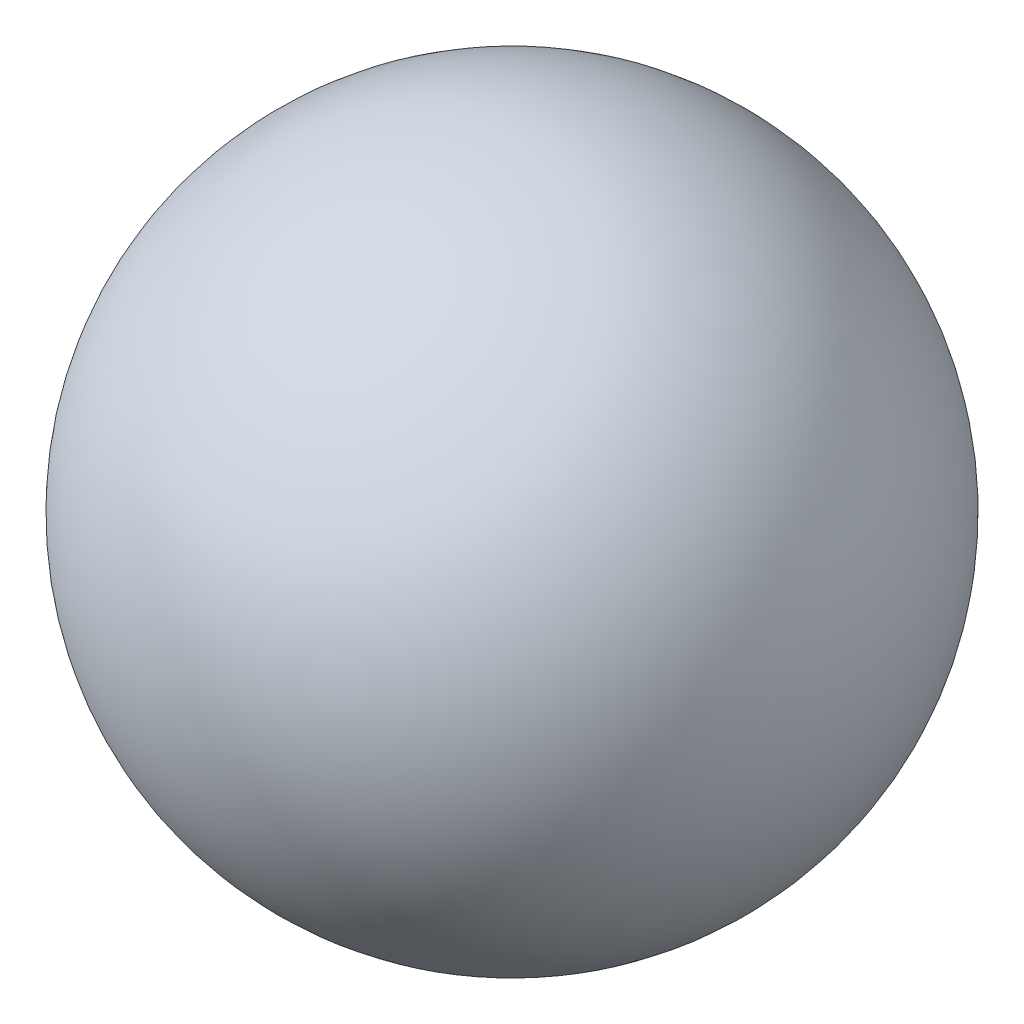
SolidWorks part; units mm, degrees
ref_plane "Front Plane" through (0, 0, 0) normal (0, 0, 1) x (1, 0, 0)
ref_plane "Top Plane" through (0, 0, 0) normal (0, 1, 0) x (1, 0, 0)
ref_plane "Right Plane" through (0, 0, 0) normal (1, 0, 0) x (0, 0, -1)
sketch "Sketch1" plane through (0, 0, 0) normal (1, 0, 0) x (0, 0, -1)
  line L0 (0, 20) -> (0, -20)
  arc A0 (0, 20) -> (0, -20) centre (0, 0) cw
  dimension "D1" = 20
revolve "Revolve1" add sketch "Sketch1" angle 360 about L0
sketch "Sketch2" plane through (0, 0, 0) normal (0, 1, 0) x (1, 0, 0)
  circle A0 centre (0, 0) radius 3.9688
  dimension "D1" = 7.9375
extrude "Cut-Extrude1" cut sketch "Sketch2" against normal through all and the other way blind 3
cosmetic thread "Cosmetic Thread1"
